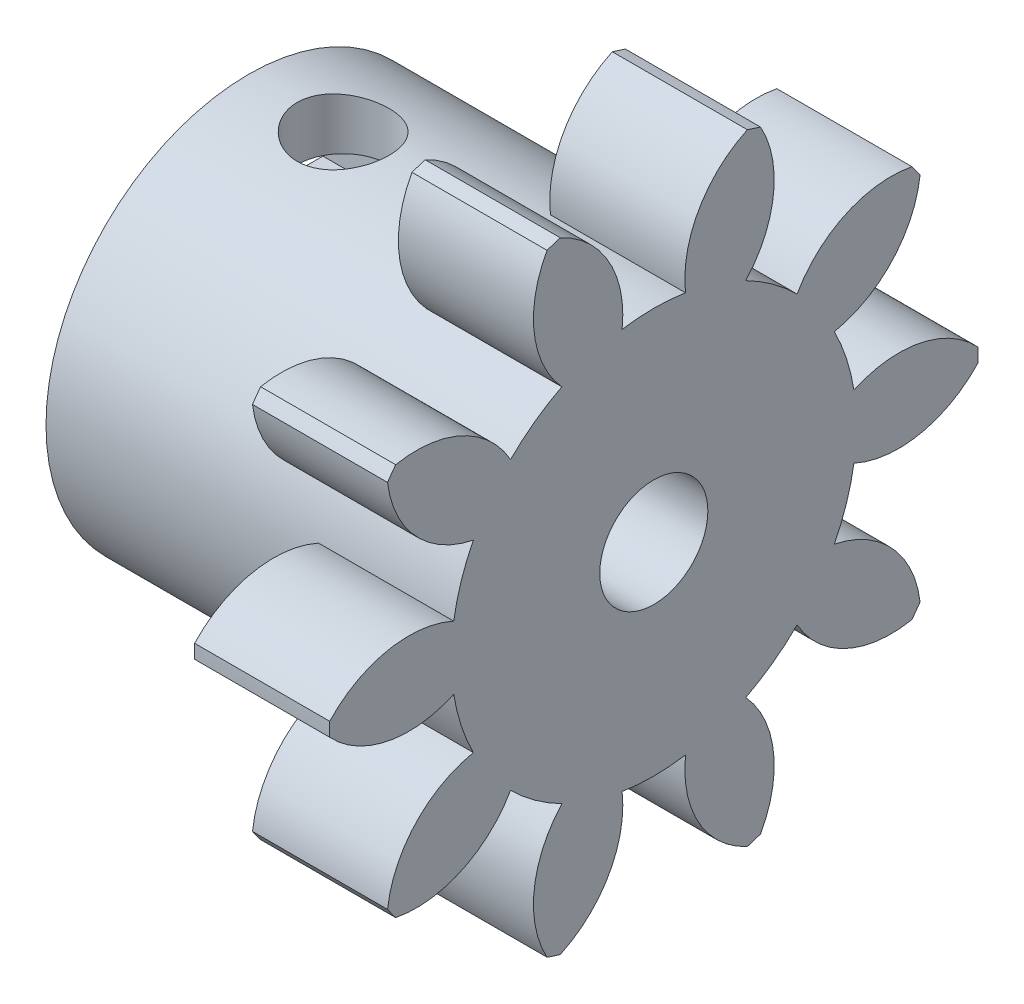
SolidWorks part; units mm, degrees
ref_plane "Plane1" through (0, 0, 0) normal (0, 0, 1) x (1, 0, 0)
ref_plane "Plane2" through (0, 0, 0) normal (0, 1, 0) x (1, 0, 0)
ref_plane "Plane3" through (0, 0, 0) normal (1, 0, 0) x (0, 0, -1)
sketch "HoldingSke" plane through (0, 0, 0) normal (0, 1, 0) x (1, 0, 0)
  line L0 (0, 0) -> (0.4924, -0.0868)
  line L1 (-15, 0) -> (100, 0) construction
  line L2 (0, 0) -> (-2.1039, 2.3779)
  line L3 (0, 0) -> (-11.863, 4.5341)
  line L4 (0, 0) -> (8.5048, 1.4996)
  line L5 (0, 0) -> (-18.7391, -6.9891)
  line L6 (0, 0) -> (-8.2896, -5.593)
  line L7 (-2.1039, 2.3779) -> (2.2011, 21.9091)
  line L8 (-76.2, 54.61) -> (-75.5, 54.61)
  line L9 (-71.009, 38.7566) -> (-53.1078, 45.2721)
  line L10 (-76.2, 71.12) -> (104.1128, 71.12)
  line L11 (0, 0) -> (-10, 0)
  line L12 (-76.2, 101.6) -> (-76.133, 101.6)
  line L13 (24.9733, 27.94) -> (52.9518, 28.4284)
  line L14 (24.9733, 27.94) -> (24.9743, 27.94)
  line L15 (24.9733, 27.94) -> (100.4006, 29.5858)
  line L16 (-63.627, -2) -> (-12.827, -2)
  circle A0 centre (0, 0) radius 2
  circle A1 centre (0, 0) radius 7.499
  circle A2 centre (0, 0) radius 25
  circle A3 centre (0, 0) radius 2
  dimension "MHD" = 14.998
  dimension "Hub_dia" = 50
  dimension "Bore" = 4
  dimension "MBD" = 4
  dimension "Num_teeth" = 10
  dimension "Pitch_radius" = 180.3128
  dimension "Pitch" = 0.5
  dimension "Width" = 10
  dimension "Overall_len" = 20
  dimension "Show_teeth" = 10
  dimension "Thickness" = 10
  dimension "OAL" = 20.0001
  dimension "T_dim" = 0.7
  dimension "Ap" = 20
  dimension "H" = 19.05
  dimension "Backlash" = 0.067
  dimension "Addendum_fac" = 1
  dimension "Dedendum_fac" = 1.25
  dimension "Clearance_fac" = 0.25
  dimension "Dedendum_add" = 0.001
  dimension "Module" = 2
sketch "BasProSke" plane through (0, 0, 0) normal (0, 1, 0) x (1, 0, 0)
  line L0 (-10, 0) -> (60, 0) construction
  line L1 (0, 0) -> (0, 12)
  line L2 (0, 0) -> (10, 0)
  line L3 (10, 0) -> (10, 12)
  line L4 (10, 12) -> (0, 12)
  dimension "Diameter" = 24
  dimension "Thickness" = 10
revolve "Base-Revolve" add sketch "BasProSke" angle 360 about L0
sketch "TooCutSke" plane through (0, 0, 0) normal (1, 0, 0) x (0, 0, -1)
  line L1 (0, 0) -> (0, 107) construction
  line L2 (0, 0) -> (-1.6814, 9.8576) construction
  line L3 (0, 0) -> (-6.1153, 18.8209) construction
  line L4 (-1.6814, 9.8576) -> (-3.0576, 9.4105) construction
  arc A0 (1.1737, 7.4066) -> (-1.1737, 7.4066) centre (0, 0) ccw
  arc A1 (3.4979, 11.5054) -> (-3.4979, 11.5054) centre (0, 0) ccw
  circle A2 centre (0, 0) radius 10 construction
  circle A3 centre (0, 0) radius 9.3969 construction
  arc A4 (-1.1737, 7.4066) -> (-3.4979, 11.5054) centre (-5.1477, 7.8615) ccw
  arc A5 (3.4979, 11.5054) -> (1.1737, 7.4066) centre (5.1477, 7.8615) ccw
  dimension "Root_dia" = 14.998
  dimension "Overcut_dia" = 24.0508
  dimension "Pitch_dia" = 20
  dimension "Base_dia" = 18.7939
  dimension "Flank_rad" = 4
  dimension "Half_ang" = 18
  dimension "Half_CT" = 1.4471
extrude "ToothCut" cut sketch "TooCutSke" along normal through all
fillet "Breaks" [suppressed] radius 0.04 tangent propagation no
fillet "RootFillets" [suppressed] radius 0.501
pattern_circular "TeethCuts" count 10 every 36 about axis through (-10, 0, 0) along (1, 0, 0) of "ToothCut", "RootFillets", "Breaks"
sketch "HubNeaOneSke" plane through (0, 0, 0) normal (-1, 0, 0) x (0, 0, 1)
  circle A0 centre (0, 0) radius 7.499
  dimension "Diameter" = 14.998
extrude "HubNearOne" add sketch "HubNeaOneSke" along normal blind 10.0001
sketch "HubNeaBotSke" plane through (0, 0, 0) normal (-1, 0, 0) x (0, 0, 1)
  circle A0 centre (0, 0) radius 7.499
  dimension "Diameter" = 14.998
extrude "HubNearBoth" [suppressed] add sketch "HubNeaBotSke" along normal blind 5
ref_plane "FarPln" through (10, 0, 0) normal (1, 0, 0) x (0, 0, -1)
sketch "HubFarSke" plane through (10, 0, 0) normal (1, 0, 0) x (0, 0, -1)
  circle A0 centre (0, 0) radius 7.499
  dimension "Diameter" = 14.998
extrude "HubFar" [suppressed] add sketch "HubFarSke" along normal blind 5
sketch "BorSke" plane through (0, 0, 0) normal (1, 0, 0) x (0, 0, -1)
  circle A0 centre (0, 0) radius 2
  dimension "Diameter" = 4
extrude "Bore" cut sketch "BorSke" along normal mid plane 40.0001
sketch "KeySke" plane through (0, 0, 0) normal (1, 0, 0) x (0, 0, -1)
  line L0 (-0.8, 0) -> (-0.8, 2.7)
  line L1 (-0.8, 2.7) -> (0.8, 2.7)
  line L2 (0.8, 2.7) -> (0.8, 0)
  line L3 (0, 0) -> (0, 34) construction
  line L4 (-0.8, 0) -> (0.8, 0)
  dimension "Offset" = 2.7
  dimension "Width" = 1.6
extrude "Keyway" [suppressed] cut sketch "KeySke" along normal mid plane 40.0001
pattern_circular "Keyway2" [suppressed] count 2 every 90 about axis through (-10, 0, 0) along (1, 0, 0)
sketch "Esquisse1" plane through (-10.0001, 0, 0) normal (-1, 0, 0) x (0, 0, 1)
  line L0 (0, 0) -> (0, 6.8885) construction
  line L1 (-2.75, 5.5) -> (2.75, 5.5)
  line L2 (-2.75, 5.5) -> (-2.75, 3.5)
  line L3 (-2.75, 3.5) -> (2.75, 3.5)
  line L4 (2.75, 5.5) -> (2.75, 3.5)
  line L5 (-2.75, 5.5) -> (2.75, 3.5) construction
  line L6 (-2.75, 3.5) -> (2.75, 5.5) construction
  point P0 (0, 4.5)
  dimension "D1" = 5.5
  dimension "D2" = 2
  dimension "D3" = 4.5
extrude "Enlèv. mat.-Extru.1" cut sketch "Esquisse1" against normal blind 7
hole_wizard "Dégagement M31" positions "Esquisse5" profile "Esquisse4" hole size "M3" standard "Ansi Métrique"
sketch "Esquisse5" plane through (0, 3.5, 0) normal (0, 1, 0) x (-1, 0, 0)
  line L0 (10.0001, -2.75) -> (10.0001, 2.75) construction
  line L1 (3.0001, -2.75) -> (10.0001, -2.75) construction
  point P0 (6.5001, 0)
  dimension "D1" = 3.5
  dimension "D2" = 2.75
sketch "Esquisse4" plane through (-6.5001, 3.5, 0) normal (1, 0, 0) x (0, 0, 1)
  line L0 (0, 0) -> (0, 4.0215)
  line L1 (0, 4.0215) -> (1.7, 3)
  line L2 (1.7, 3) -> (1.7, 0)
  line L5 (1.7, 0) -> (0, 0)
  line L10 (0, 4.0215) -> (-1.7, 3) construction
  line L11 (0, -6.35) -> (0, 107.95) construction
  dimension "Diamètre du perçage" = 3.4
  dimension "Profondeur du perçage" = 3
  dimension "Angle de pointe" = 118
sketch "Esquisse6" plane through (0, 3.5, 0) normal (0, 1, 0) x (-1, 0, 0)
  circle A1 centre (6.5001, 0) radius 1.7
extrude "Enlèv. mat.-Extru.2" cut sketch "Esquisse6" along normal up to next
sketch "Esquisse7" plane through (10, 0, 0) normal (1, 0, 0) x (0, 0, -1)
  circle A0 centre (0, 0) radius 12
  dimension "D1" = 24
extrude "Enlèv. mat.-Extru.3" cut sketch "Esquisse7" against normal blind 5
equation "' \"Module@HoldingSke\" = 6.35"
equation "' \"Num_teeth@HoldingSke\" = 12"
equation "' \"Ap@HoldingSke\" =  20"
equation "' \"Width@HoldingSke\" = 0.5 * 25.4"
equation "' \"Hub_dia@HoldingSke\"= 1 * 25.4"
equation "' \"Overall_len@HoldingSke\" = 1.0 * 25.4"
equation "' \"Bore@HoldingSke\" = 0.75 * 25.4"
equation "' \"T_dim@HoldingSke\" = 0.1 * 25.4"
equation "' \"Width@KeySke\" = 0.25 * 25.4"
equation "' \"Show_teeth@HoldingSke\" = 13"
equation "' \"Backlash@HoldingSke\" = 0.009 * 25.4"
equation "' \"Addendum_fac@HoldingSke\" = 1.0"
equation "' \"Dedendum_fac@HoldingSke\" = 1.25"
equation "' \"Dedendum_add@HoldingSke\" = 0.00005 * 25.4"
equation "' \"Clearance_fac@HoldingSke\" = 0.25"
equation "\"Pitch@HoldingSke\" = 1 / \"Module@HoldingSke\""
equation "\"Overcut_dia@TooCutSke\" = (\"Num_teeth@HoldingSke\" + 2 * \"Addendum_fac@HoldingSke\") / \"Pitch@HoldingSke\" + 0.002 * 25.4"
equation "\"Pitch_dia@TooCutSke\" = \"Num_teeth@HoldingSke\" / \"Pitch@HoldingSke\""
equation "\"Base_dia@TooCutSke\" = \"Num_teeth@HoldingSke\" / \"Pitch@HoldingSke\" * cos((\"Ap@HoldingSke\"  * 3.14159265 / 180))"
equation "\"Root_dia@TooCutSke\" = (\"Num_teeth@HoldingSke\" + 2) / \"Pitch@HoldingSke\" - 2 * (\"Addendum_fac@HoldingSke\" + \"Dedendum_fac@HoldingSke\") / \"Pitch@HoldingSke\" - \"Dedendum_add@HoldingSke\" * 2"
equation "\"Half_ang@TooCutSke\" = 180 / \"Num_teeth@HoldingSke\""
equation "\"Half_CT@TooCutSke\" = \"Num_teeth@HoldingSke\" / \"Pitch@HoldingSke\" * sin((3.14159265 / 2 / \"Num_teeth@HoldingSke\")) / 2 - 7 * \"Backlash@HoldingSke\" / 4"
equation "\"Flank_rad@TooCutSke\" = \"Num_teeth@HoldingSke\" / \"Pitch@HoldingSke\" / 5"
equation "\"Radius@RootFillets\" = \"Clearance_fac@HoldingSke\" / \"Pitch@HoldingSke\" + \"Dedendum_add@HoldingSke\""
equation "\"Break_rad@Breaks\" = 0.02 / \"Pitch@HoldingSke\""
equation "\"Thickness@HoldingSke\" = \"Width@HoldingSke\""
equation "\"OAL@HoldingSke\" = \"Thickness@HoldingSke\""
equation "\"MHD@HoldingSke\" = (\"Num_teeth@HoldingSke\" + 2) / \"Pitch@HoldingSke\" - 2 * (\"Addendum_fac@HoldingSke\" + \"Dedendum_fac@HoldingSke\")  / \"Pitch@HoldingSke\" - \"Dedendum_add@HoldingSke\" * 2"
equation "\"MBD@HoldingSke\" = (\"Num_teeth@HoldingSke\" + 2) / \"Pitch@HoldingSke\" - 2 * (\"Addendum_fac@HoldingSke\" + \"Dedendum_fac@HoldingSke\")  / \"Pitch@HoldingSke\" - \"Dedendum_add@HoldingSke\" * 2 - 0.002 * 25.4"
equation "\"MHD@HoldingSke\" = ((sgn( \"MHD@HoldingSke\" - \"Hub_dia@HoldingSke\" )-1)*( \"MHD@HoldingSke\" - \"Hub_dia@HoldingSke\" ))/-2+ \"Hub_dia@HoldingSke\""
equation "\"MBD@HoldingSke\" = ((sgn( \"MBD@HoldingSke\" - \"Bore@HoldingSke\" )-1)*( \"MBD@HoldingSke\" - \"Bore@HoldingSke\" ))/-2+ \"Bore@HoldingSke\""
equation "\"OAL@HoldingSke\" = ((sgn( \"OAL@HoldingSke\" - \"Overall_len@HoldingSke\" )+1)*( \"OAL@HoldingSke\" - \"Overall_len@HoldingSke\" ))/2 + \"Overall_len@HoldingSke\" + 0.000002 * 25.4"
equation "\"Num_teeth@TeethCuts\" = int( \"Show_teeth@HoldingSke\" ) + 1"
equation "\"Num_teeth@TeethCuts\" = ((sgn( \"Num_teeth@TeethCuts\" - \"Num_teeth@HoldingSke\" )-1)*( \"Num_teeth@TeethCuts\" - \"Num_teeth@HoldingSke\" ))/-2+ \"Num_teeth@HoldingSke\""
equation "\"Num_teeth@TeethCuts\" = ((sgn( \"Num_teeth@TeethCuts\" - 2.0)+1)*( \"Num_teeth@TeethCuts\" - 2.0))/2 +2.0"
equation "\"Angle@TeethCuts\" = 360.0 / \"Num_teeth@HoldingSke\""
equation "\"Diameter@BasProSke\" = (\"Num_teeth@HoldingSke\" + 2 * \"Addendum_fac@HoldingSke\") / \"Pitch@HoldingSke\""
equation "\"Thickness@BasProSke\"  = \"Thickness@HoldingSke\""
equation "' \"Fillet_rad@BasProSke\" =  \"Thickness@HoldingSke\" * 0.05"
equation "\"MHD@HoldingSke\" = ((sgn( \"MHD@HoldingSke\" - \"Root_dia@TooCutSke\" )-1)*( \"MHD@HoldingSke\" - \"Root_dia@TooCutSke\" ))/-2+ \"Root_dia@TooCutSke\""
equation "\"Diameter@HubNeaOneSke\" = \"MHD@HoldingSke\""
equation "\"Length@HubNearOne\" = \"OAL@HoldingSke\" - \"Thickness@BasProSke\""
equation "\"Diameter@HubNeaBotSke\" = \"MHD@HoldingSke\""
equation "\"Length@HubNearBoth\" = ( \"OAL@HoldingSke\" - \"Thickness@BasProSke\" ) / 2.0"
equation "\"Thickness@FarPln\" = \"Thickness@BasProSke\""
equation "\"Diameter@HubFarSke\" = \"MHD@HoldingSke\""
equation "\"Length@HubFar\" = ( \"OAL@HoldingSke\" - \"Thickness@BasProSke\" ) / 2.0"
equation "\"Diameter@BorSke\" = \"MBD@HoldingSke\""
equation "\"D1@Bore\" = \"OAL@HoldingSke\" * 2.0"
equation "\"D1@Keyway\" = \"OAL@HoldingSke\" * 2.0"
equation "\"Offset@KeySke\" = \"T_dim@HoldingSke\" + \"MBD@HoldingSke\" / 2.0"
